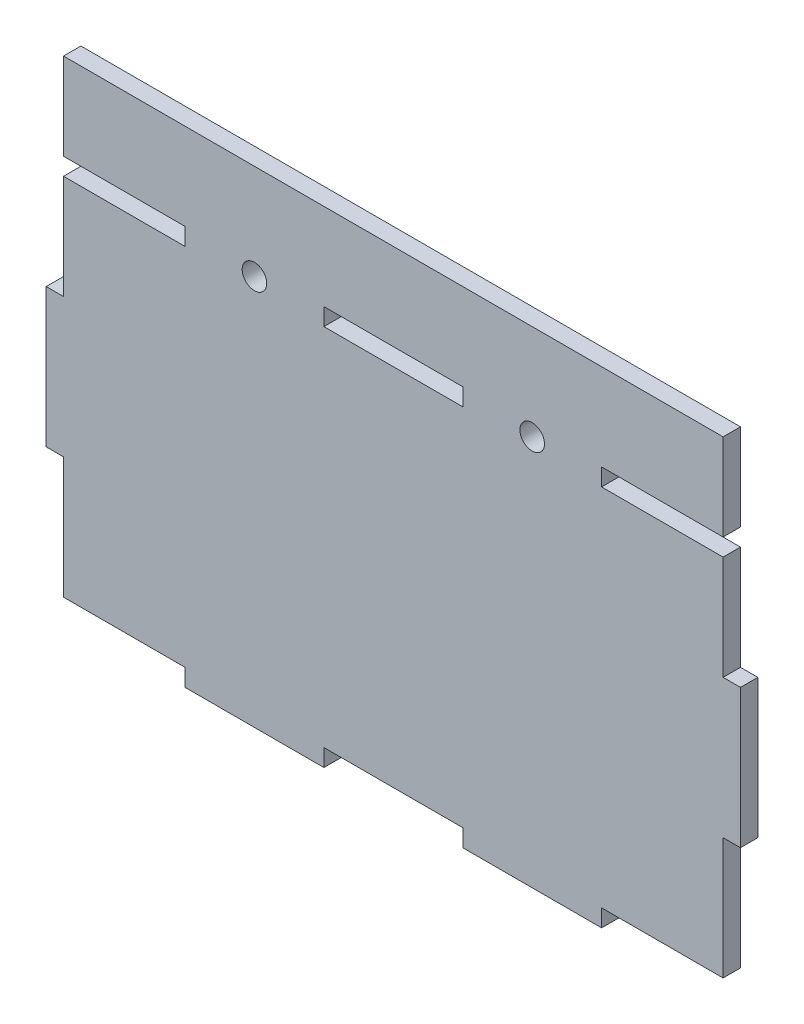
SolidWorks part; units mm, degrees
ref_plane "Front Plane" through (0, 0, 0) normal (0, 0, 1) x (1, 0, 0)
ref_plane "Top Plane" through (0, 0, 0) normal (0, 1, 0) x (1, 0, 0)
ref_plane "Right Plane" through (0, 0, 0) normal (1, 0, 0) x (0, 0, -1)
sketch "Sketch1" plane through (0, 0, 0) normal (0, 0, 1) x (1, 0, 0)
  line L1 (0, 0) -> (127, 0)
  line L2 (0, 0) -> (0, 88.9)
  line L3 (0, 88.9) -> (127, 88.9)
  line L4 (127, 0) -> (127, 88.9)
  dimension "D1" = 127
  dimension "D2" = 88.9
extrude "Boss-Extrude1" add sketch "Sketch1" along normal blind 3.175
sketch "Sketch5" plane through (0, 0, 3.175) normal (0, 0, 1) x (1, 0, 0)
  line L1 (0, 0) -> (3.175, 0)
  line L2 (0, 0) -> (0, 25.4)
  line L3 (0, 25.4) -> (3.175, 25.4)
  line L4 (3.175, 0) -> (3.175, 25.4)
  dimension "D1" = 25.4
  dimension "D2" = 3.175
extrude "Cut-Extrude4" cut sketch "Sketch5" against normal blind 6.35
sketch "Sketch6" plane through (0, 0, 3.175) normal (0, 0, 1) x (1, 0, 0)
  line L1 (0, 0) -> (25.4, 0)
  line L2 (0, 0) -> (0, 3.175)
  line L3 (0, 3.175) -> (25.4, 3.175)
  line L4 (25.4, 0) -> (25.4, 3.175)
  dimension "D1" = 3.175
  dimension "D2" = 25.4
extrude "Cut-Extrude5" cut sketch "Sketch6" against normal blind 6.35
pattern_linear "LPattern5" count 2 spacing 50.8 along (0, 1, 0) count 2 spacing 123.825 along (1, 0, 0) of "Cut-Extrude4"
pattern_linear "LPattern6" count 3 spacing 50.8 along (1, 0, 0) count 2 spacing 69.85 along (0, 1, 0) of "Cut-Extrude5"
hole_wizard "#8 Clearance Hole1" positions "Sketch10" profile "Sketch9" hole size "#8" standard "ANSI Inch"
sketch "Sketch10" plane through (0, 0, 3.175) normal (0, 0, 1) x (1, 0, 0)
  line L2 (25.4, 69.85) -> (25.4, 73.025) construction
  line L3 (76.2, 73.025) -> (50.8, 73.025) construction
  line L4 (76.2, 69.85) -> (76.2, 73.025) construction
  point P0 (38.1, 71.4375)
  point P2 (88.9, 71.4375)
  point P10 (25.4, 71.4375)
  dimension "D1" = 12.7
  dimension "D3" = 12.7
  dimension "D4" = 1.5875
sketch "Sketch9" plane through (38.1, 71.4375, 3.175) normal (1, 0, 0) x (0, -1, 0)
  line L0 (0, 0) -> (0, 11.5107)
  line L1 (0, 11.5107) -> (2.2479, 10.16)
  line L2 (2.2479, 10.16) -> (2.2479, 0)
  line L5 (2.2479, 0) -> (0, 0)
  line L10 (0, 11.5107) -> (-2.2479, 10.16) construction
  line L11 (0, -6.35) -> (0, 107.95) construction
  dimension "Hole Dia." = 4.4958
  dimension "Hole Depth" = 10.16
  dimension "Drill Angle" = 118
sketch "Sketch11" plane through (0, 0, 3.175) normal (0, 0, 1) x (1, 0, 0)
  line L1 (0, 88.9) -> (3.175, 88.9)
  line L2 (0, 88.9) -> (0, 76.2)
  line L3 (0, 76.2) -> (3.175, 76.2)
  line L4 (3.175, 88.9) -> (3.175, 76.2)
  line L5 (127, 88.9) -> (123.825, 88.9)
  line L6 (127, 88.9) -> (127, 76.2)
  line L7 (127, 76.2) -> (123.825, 76.2)
  line L8 (123.825, 88.9) -> (123.825, 76.2)
extrude "Cut-Extrude6" cut sketch "Sketch11" against normal blind 7.62
